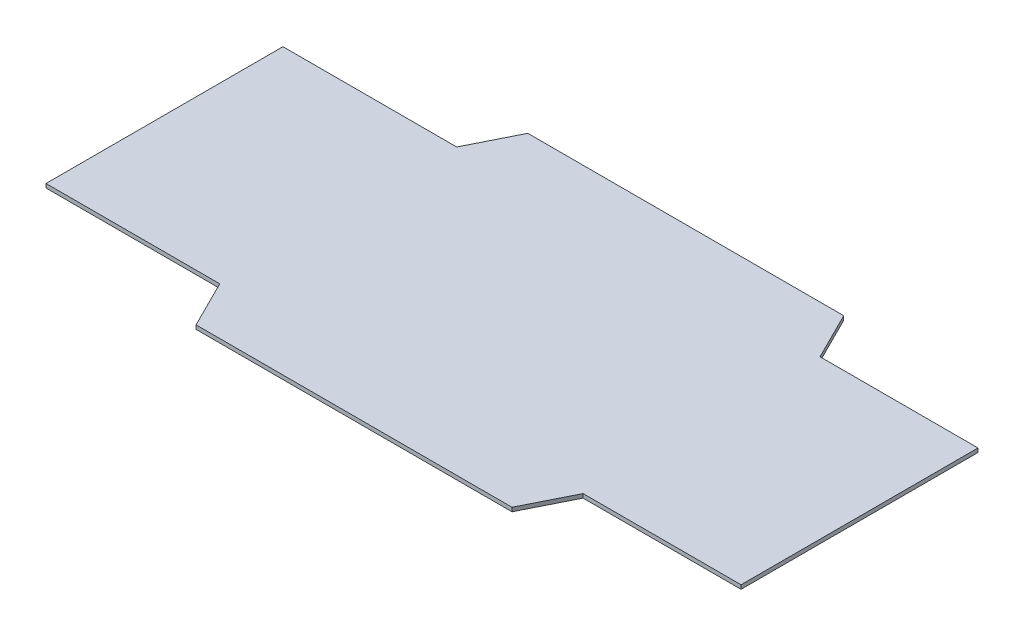
SolidWorks part; units mm, degrees
ref_plane "Front Plane" through (0, 0, 0) normal (0, 0, 1) x (1, 0, 0)
ref_plane "Top Plane" through (0, 0, 0) normal (0, 1, 0) x (1, 0, 0)
ref_plane "Right Plane" through (0, 0, 0) normal (1, 0, 0) x (0, 0, -1)
sketch "Sketch3" plane through (0, 0, 0) normal (0, 1, 0) x (1, 0, 0)
  line L0 (-279.4, 95.25) -> (-139.7, 95.25)
  line L1 (-279.4, -133.35) -> (279.4, -133.35) construction
  line L2 (-279.4, -133.35) -> (-279.4, 133.35) construction
  line L3 (-279.4, 133.35) -> (279.4, 133.35) construction
  line L4 (279.4, -133.35) -> (279.4, 133.35) construction
  line L5 (-279.4, -133.35) -> (279.4, 133.35) construction
  line L6 (-279.4, 133.35) -> (279.4, -133.35) construction
  line L7 (-279.4, -95.25) -> (279.4, -95.25) construction
  line L8 (-279.4, -95.25) -> (-279.4, 95.25) construction
  line L9 (-279.4, 95.25) -> (279.4, 95.25) construction
  line L10 (279.4, -95.25) -> (279.4, 95.25) construction
  line L13 (-139.7, 95.25) -> (-120.65, 133.35)
  line L14 (-120.65, 133.35) -> (133.35, 133.35)
  line L15 (133.35, 133.35) -> (152.4, 95.25)
  line L16 (152.4, 95.25) -> (279.4, 95.25)
  line L17 (-279.4, 95.25) -> (-279.4, -95.25)
  line L18 (279.4, 95.25) -> (279.4, -95.25)
  line L19 (-279.4, 0) -> (279.4, 0) construction
  line L20 (152.4, -95.25) -> (279.4, -95.25)
  line L21 (133.35, -133.35) -> (152.4, -95.25)
  line L22 (-120.65, -133.35) -> (133.35, -133.35)
  line L23 (-139.7, -95.25) -> (-120.65, -133.35)
  line L24 (-279.4, -95.25) -> (-139.7, -95.25)
  point P0 (0, 0)
  point P6 (0, 0)
  dimension "D1" = 266.7
  dimension "D2" = 558.8
  dimension "D3" = 190.5
  dimension "D4" = 127
  dimension "D5" = 139.7
  dimension "D6" = 254
extrude "Boss-Extrude1" add sketch "Sketch3" along normal mid plane 3.175
sketch "Sketch5" plane through (0, -1.5875, 0) normal (0, -1, 0) x (1, 0, 0)
  line L0 (-202.3532, 0) -> (279.4, 0) construction
  line L1 (-63.5, 25.4) -> (76.2, 25.4)
  line L2 (-63.5, 25.4) -> (-63.5, 88.9)
  line L3 (-63.5, 88.9) -> (76.2, 88.9)
  line L4 (76.2, 25.4) -> (76.2, 88.9)
  line L5 (-63.5, 25.4) -> (76.2, 88.9) construction
  line L6 (-63.5, 88.9) -> (76.2, 25.4) construction
  line L7 (279.4, 95.25) -> (279.4, -95.25) construction
  line L8 (-120.65, 133.35) -> (133.35, 133.35) construction
  line L9 (-120.65, 133.35) -> (133.35, 133.35) construction
  line L10 (6.35, 133.35) -> (6.35, 88.9) construction
  line L11 (-63.5, -88.9) -> (76.2, -88.9)
  line L12 (76.2, -25.4) -> (76.2, -88.9)
  line L13 (-63.5, -25.4) -> (76.2, -25.4)
  line L14 (-63.5, -25.4) -> (-63.5, -88.9)
  point P4 (6.35, 57.15)
  dimension "D1" = 63.5
  dimension "D2" = 139.7
  dimension "D3" = 44.45
sketch "Sketch6" plane through (0, 1.5875, 0) normal (0, 1, 0) x (1, 0, 0)
  line L0 (-279.4, 95.25) -> (-139.7, 95.25) construction
  line L1 (-120.65, 133.35) -> (-139.7, 95.25) construction
  line L2 (-139.7, 95.25) -> (-279.4, 95.25) construction
  line L3 (-139.7, 95.25) -> (-120.65, 133.35) construction
  line L4 (-120.65, 133.35) -> (133.35, 133.35) construction
  line L5 (133.35, 133.35) -> (152.4, 95.25) construction
  line L6 (152.4, 95.25) -> (279.4, 95.25) construction
  line L7 (279.4, 95.25) -> (279.4, -95.25) construction
  line L8 (279.4, -95.25) -> (152.4, -95.25) construction
  line L9 (133.35, -133.35) -> (152.4, -95.25) construction
  line L10 (152.4, -95.25) -> (279.4, -95.25) construction
  line L11 (152.4, -95.25) -> (133.35, -133.35) construction
  line L12 (133.35, -133.35) -> (-120.65, -133.35) construction
  line L13 (-120.65, -133.35) -> (-139.7, -95.25) construction
  line L14 (-139.7, -95.25) -> (-279.4, -95.25) construction
  line L15 (-279.4, -95.25) -> (-279.4, 95.25) construction
  line L16 (-276.225, 92.075) -> (-137.7377, 92.075)
  line L17 (-137.7377, 92.075) -> (-118.6877, 130.175)
  line L18 (-118.6877, 130.175) -> (131.3877, 130.175)
  line L19 (131.3877, 130.175) -> (150.4377, 92.075)
  line L20 (150.4377, 92.075) -> (276.225, 92.075)
  line L21 (276.225, 92.075) -> (276.225, -92.075)
  line L22 (276.225, -92.075) -> (150.4377, -92.075)
  line L23 (150.4377, -92.075) -> (131.3877, -130.175)
  line L24 (131.3877, -130.175) -> (-118.6877, -130.175)
  line L25 (-118.6877, -130.175) -> (-137.7377, -92.075)
  line L26 (-137.7377, -92.075) -> (-276.225, -92.075)
  line L27 (-276.225, -92.075) -> (-276.225, 92.075)
  dimension "D1" = 3.175
